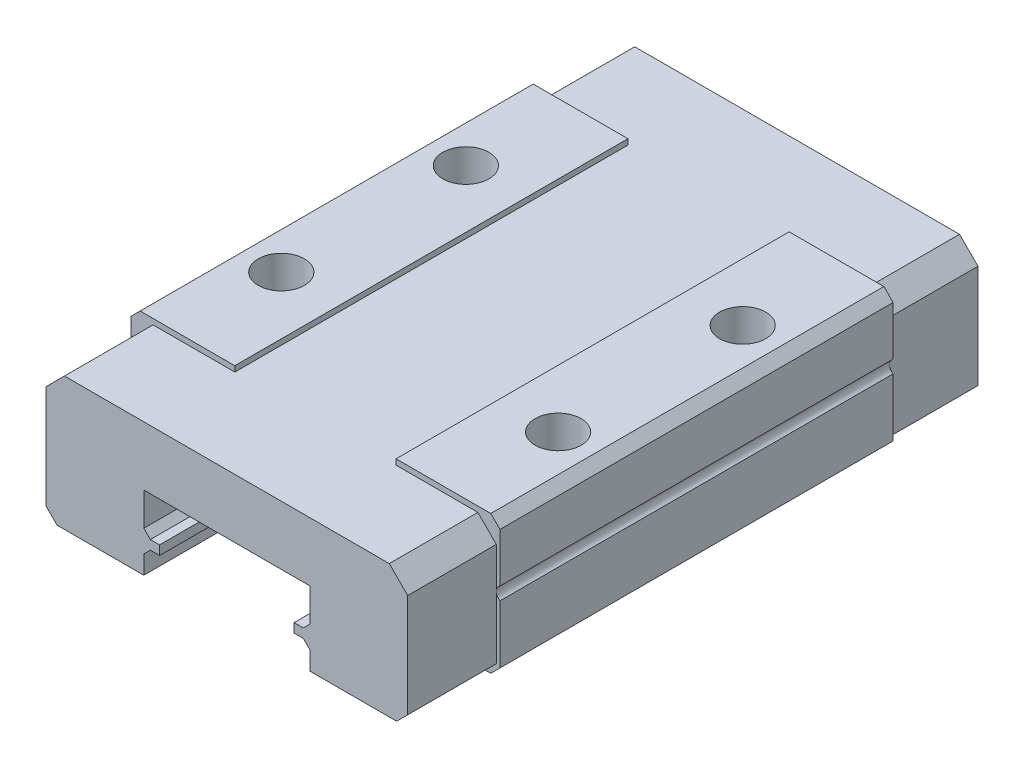
SolidWorks part; units mm, degrees
material "AISI 1020 钢，冷轧"
ref_plane "前视基准面" through (0, 0, 0) normal (0, 0, 1) x (1, 0, 0)
ref_plane "上视基准面" through (0, 0, 0) normal (0, 1, 0) x (1, 0, 0)
ref_plane "右视基准面" through (0, 0, 0) normal (1, 0, 0) x (0, 0, -1)
sketch "草图1" plane through (0, 0, 0) normal (0, 0, 1) x (1, 0, 0)
  line L0 (0, 0) -> (0, 18.7331) construction
  line L1 (-10, 0) -> (-10, 7.5)
  line L2 (4.5, 0) -> (4.5, 1)
  line L3 (4.5, 1) -> (4.1464, 1.3536)
  line L4 (4.1464, 1.3536) -> (3.6464, 1.3536)
  line L5 (3.6464, 1.3536) -> (3.6464, 1.8536)
  line L6 (3.6464, 1.8536) -> (4.1464, 1.8536)
  line L7 (4.1464, 1.8536) -> (4.5, 2.2071)
  line L8 (4.5, 2.2071) -> (4.5, 4)
  line L9 (4.5, 4) -> (-4.5, 4)
  line L10 (4.5, 0) -> (10, 0)
  line L11 (10, 0) -> (10, 7.5)
  line L12 (10, 7.5) -> (-10, 7.5)
  line L13 (-4.5, 0) -> (-10, 0)
  line L14 (-4.5, 2.2071) -> (-4.5, 4)
  line L15 (-4.1464, 1.8536) -> (-4.5, 2.2071)
  line L16 (-3.6464, 1.8536) -> (-4.1464, 1.8536)
  line L17 (-3.6464, 1.3536) -> (-3.6464, 1.8536)
  line L18 (-4.1464, 1.3536) -> (-3.6464, 1.3536)
  line L19 (-4.5, 1) -> (-4.1464, 1.3536)
  line L20 (-4.5, 0) -> (-4.5, 1)
  point P16 (0, 7.5)
  point P19 (0, 4)
  dimension "D1" = 4.5
  dimension "D2" = 1
  dimension "D3" = 0.5
  dimension "D4" = 0.5
  dimension "D5" = 0.5
  dimension "D6" = 4
  dimension "D7" = 10
  dimension "D8" = 7.5
extrude "凸台-拉伸1" add sketch "草图1" against normal blind 30.9
sketch "草图2" plane through (0, 7.5, 0) normal (0, 1, 0) x (1, 0, 0)
  line L0 (0, 30.9) -> (0, 0) construction
  line L1 (10, 30.9) -> (-10, 30.9) construction
  line L2 (10, 15.45) -> (-10, 15.45) construction
  line L3 (10, 30.9) -> (10, 0) construction
  line L4 (-10, 30.9) -> (-10, 0) construction
hole_wizard "M3 螺纹孔1" positions "草图4" profile "草图3" tap size "M3" standard "Gb"
sketch "草图4" plane through (0, 7.5, 0) normal (0, 1, 0) x (1, 0, 0)
  line L0 (0, 30.9) -> (0, 0) construction
  line L1 (10, 15.45) -> (-10, 15.45) construction
  point P0 (7.5, 20.45)
  dimension "D1" = 7.5
  dimension "D2" = 5
sketch "草图3" plane through (7.5, 7.5, -20.45) normal (1, 0, 0) x (0, 0, 1)
  line L0 (0, 0) -> (0, 3.7511)
  line L1 (0, 3.7511) -> (1.25, 3)
  line L2 (1.25, 3) -> (1.25, 0)
  line L5 (1.25, 0) -> (0, 0)
  line L10 (0, 3.7511) -> (-1.25, 3) construction
  line L11 (0, -6.35) -> (0, 107.95) construction
  dimension "螺纹孔钻头直径" = 2.5
  dimension "螺纹孔钻头深度" = 3
  dimension "导头角度" = 118
cosmetic thread "孔螺蚊线1" parameters "D1"=3, "D2"=3
ref_plane "基准面1" through (0, 0, -15.45) normal (0, 0, -1) x (-1, 0, 0)
ref_plane "基准面2" through (0, 0, 0) normal (-1, 0, 0) x (0, 0, 1)
mirror "镜向1" about plane through (0, 0, -15.45) normal (0, 0, -1) of "M3 螺纹孔1"
mirror "镜向2" about plane through (0, 0, 0) normal (-1, 0, 0) of "镜向1"
chamfer "倒角1" distance 0.5 angle 45 2 edges at (10, 7.5, -15.45) (-10, 7.5, -15.45)
sketch "草图5" plane through (0, 7.5, 0) normal (0, 1, 0) x (1, 0, 0)
  line L0 (-9.5, 26.1) -> (-4.3686, 26.1)
  line L1 (-9.5, 30.9) -> (-9.5, 0) construction
  line L2 (-4.3686, 26.1) -> (-4.3686, 4.8)
  line L3 (-4.3686, 4.8) -> (-9.5, 4.8)
  line L4 (0, 30.9) -> (0, -1.0585) construction
  line L5 (9.5, 30.9) -> (-9.5, 30.9) construction
  line L6 (4.3686, 4.8) -> (9.5, 4.8)
  line L7 (4.3686, 26.1) -> (4.3686, 4.8)
  line L8 (9.5, 26.1) -> (4.3686, 26.1)
  line L9 (9.5, 0) -> (-9.5, 0) construction
  line L10 (-9.5, 26.1) -> (-10, 26.1)
  line L11 (-10, 0) -> (-10, 30.9) construction
  line L12 (-10, 26.1) -> (-10, 30.9)
  line L13 (-10, 30.9) -> (10, 30.9)
  line L14 (10, 30.9) -> (10, 26.1)
  line L15 (10, 30.9) -> (10, 0) construction
  line L16 (10, 26.1) -> (9.5, 26.1)
  line L17 (9.5, 4.8) -> (10, 4.8)
  line L18 (10, 4.8) -> (10, 0)
  line L19 (10, 0) -> (-10, 0)
  line L20 (-10, 0) -> (-10, 4.8)
  line L21 (-10, 4.8) -> (-9.5, 4.8)
  dimension "D1" = 4.8
  dimension "D2" = 4.8
extrude "切除-拉伸1" cut sketch "草图5" against normal blind 0.3
sketch "草图6" plane through (0, 7.2, 0) normal (0, 1, 0) x (1, 0, 0)
  line L0 (-10, 30.9) -> (-9.8, 30.9)
  line L1 (9.8, 30.9) -> (-9.8, 30.9) construction
  line L2 (-9.8, 30.9) -> (-9.8, 26.1)
  line L3 (-9.8, 26.1) -> (-10, 26.1)
  line L4 (-10, 0) -> (-10, 30.9) construction
  line L5 (-10, 26.1) -> (-10, 30.9)
  line L6 (0, 30.9) -> (0, 0) construction
  line L7 (-10, 15.45) -> (10, 15.45) construction
  line L8 (10, 30.9) -> (10, 0) construction
  line L9 (10, 26.1) -> (10, 30.9)
  line L10 (9.8, 26.1) -> (10, 26.1)
  line L11 (9.8, 30.9) -> (9.8, 26.1)
  line L12 (10, 30.9) -> (9.8, 30.9)
  line L13 (10, 0) -> (9.8, 0)
  line L14 (9.8, 0) -> (9.8, 4.8)
  line L15 (9.8, 4.8) -> (10, 4.8)
  line L16 (10, 4.8) -> (10, 0)
  line L17 (-10, 4.8) -> (-10, 0)
  line L18 (-9.8, 4.8) -> (-10, 4.8)
  line L19 (-9.8, 0) -> (-9.8, 4.8)
  line L20 (-10, 0) -> (-9.8, 0)
extrude "切除-拉伸2" cut sketch "草图6" against normal blind 8.3
chamfer "倒角2" distance 1 angle 45 4 edges at (-9.8, 7.2, -28.5) (9.8, 7.2, -28.5) (9.8, 7.2, -2.4) (-9.8, 7.2, -2.4)
chamfer "倒角3" distance 0.6 angle 45 4 edges at (9.8, 0, -2.4) (-9.8, 0, -2.4) (-9.8, 0, -28.5) (9.8, 0, -28.5)
chamfer "倒角4" distance 0.5 angle 45 2 edges at (10, 0, -15.45) (-10, 0, -15.45)
sketch "草图7" plane through (0, 0, -26.1) normal (0, 0, -1) x (-1, 0, 0)
  line L0 (-9.8, 0.6) -> (-9.8, 6.2) construction
  line L1 (-4.5, 0) -> (-9.2, 0) construction
  circle A0 centre (-10.2, 4) radius 0.4
  dimension "D1" = 0.8
  dimension "D2" = 0.4
  dimension "D3" = 4
extrude "切除-拉伸3" cut sketch "草图7" against normal up to surface (21.3 mm away) up to face at (8.6488, 4.6273, -4.8)
